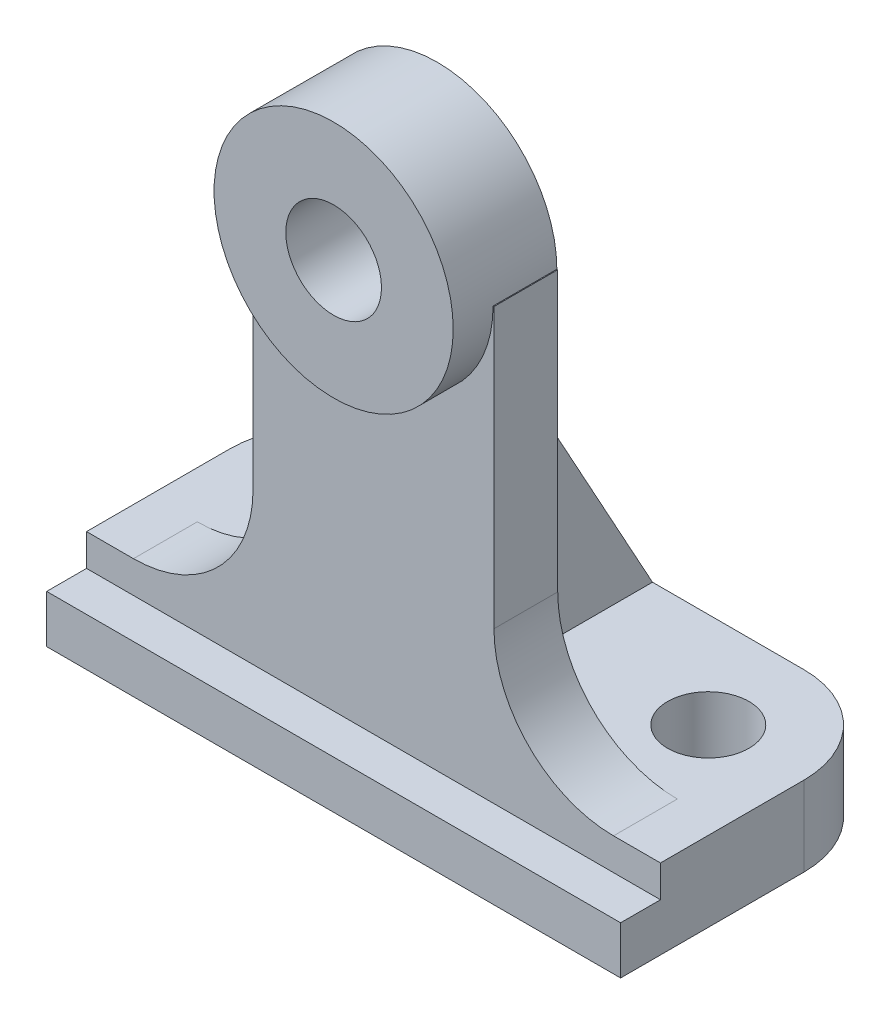
SolidWorks part; units mm, degrees
ref_plane "Front Plane" through (0, 0, 0) normal (0, 0, 1) x (1, 0, 0)
ref_plane "Top Plane" through (0, 0, 0) normal (0, 1, 0) x (1, 0, 0)
ref_plane "Right Plane" through (0, 0, 0) normal (1, 0, 0) x (0, 0, -1)
sketch "Sketch1" plane through (0, 0, 0) normal (1, 0, 0) x (0, 0, -1)
  line L1 (17.5, -5) -> (-17.5, -5)
  line L2 (17.5, -5) -> (17.5, 5)
  line L3 (17.5, 5) -> (-17.5, 5)
  line L4 (-17.5, -5) -> (-17.5, 5)
  line L5 (0, 5) -> (0, -5) construction
  line L6 (17.5, 0) -> (-17.5, 0) construction
  line L7 (-17.5, 5) -> (-12.5, 5)
  line L8 (-17.5, 5) -> (-17.5, 1)
  line L9 (-17.5, 1) -> (-12.5, 1)
  line L10 (-12.5, 5) -> (-12.5, 1)
  point P0 (0, 0)
  dimension "D1" = 10
  dimension "D2" = 35
  dimension "D3" = 5
  dimension "D4" = 4
extrude "Boss-Extrude1" add sketch "Sketch1" along normal blind 36 and the other way blind 36 contours L3 L10 L9 L4 L1 L2 region at (0, -0.1818, -0.9091)
sketch "Sketch2" plane through (0, 0, 12.5) normal (0, 0, 1) x (1, 0, 0)
  line L0 (0, 29.3775) -> (0, -15.3131) construction
  line L1 (-36, 5) -> (36, 5) construction
  line L2 (15.1114, 55) -> (-15.1114, 55)
  line L3 (15.1114, 55) -> (15.1114, 5)
  line L4 (15.1114, 5) -> (-15.1114, 5)
  line L5 (-15.1114, 55) -> (-15.1114, 5)
  line L6 (0, 5) -> (0, 55) construction
  line L7 (15.1114, 30) -> (-15.1114, 30) construction
  arc A0 (-15.1114, 55) -> (15.1114, 55) centre (0, 55) cw
  circle A1 centre (0, 55) radius 6
  circle A2 centre (0, 55) radius 15
  point P3 (0, 30)
  line M7 (36, 5) -> (-36, 5)
  dimension "D3" = 12
  dimension "D4" = 30
  dimension "D1" = 50
  dimension "D2" = 30.2229
extrude "Boss-Extrude4" add sketch "Sketch2" against normal blind 8 contours A2 L2 L5 L3 M7 | L2 A2 A1 | L2 A2 A1 region at (0, 24.3114, 12.5) region at (0, 47.9062, 12.5) region at (0, 62.0938, 12.5)
sketch "Sketch4" plane through (0, 0, 12.5) normal (0, 0, 1) x (1, 0, 0)
  circle A0 centre (0, 55) radius 15
extrude "Boss-Extrude5" add sketch "Sketch4" along normal blind 5
sketch "Sketch6" plane through (0, 0, 12.5) normal (0, 0, -1) x (-1, 0, 0)
  circle A0 centre (0, 55) radius 6
  dimension "D1" = 12
extrude "Cut-Extrude1" cut sketch "Sketch6" against normal through all
fillet "Fillet2" radius 15 2 edges at (-15.1114, 5, 8.5) (15.1114, 5, 8.5)
fillet "Fillet3" radius 12 2 edges at (36, 0, -17.5) (-36, 0, -17.5)
hole_wizard "M12 Tapped Hole1" positions "Sketch7" profile "Sketch8" tap size "M12" standard "ISO" end condition through all
sketch "Sketch7" plane through (0, 5, 0) normal (0, 1, 0) x (1, 0, 0)
  point P0 (-24, 5.5)
  point P3 (24, 5.5)
sketch "Sketch8" plane through (-24, 5, -5.5) normal (1, 0, 0) x (0, 0, 1)
  line L0 (0, 0) -> (0, 10)
  line L1 (0, 10) -> (5.1, 10)
  line L2 (5.1, 10) -> (5.1, 0)
  line L5 (5.1, 0) -> (0, 0)
  line L11 (0, -6.35) -> (0, 107.95) construction
  dimension "Thru Tap Drill Dia." = 10.2
  dimension "Thru Tap Drill Depth" = 10
cosmetic thread "Hole Thread1" parameters "D2"=12
cosmetic thread "Hole Thread2" parameters "D2"=12
sketch "Sketch9" plane through (0, 0, 0) normal (1, 0, 0) x (0, 0, -1)
  line L0 (17.5, 5) -> (-4.5, 45)
  line L1 (-4.5, 55) -> (-4.5, 20) construction
  dimension "D1" = 40
rib "Rib2" sketch "Sketch9" sketch "Sketch9" thickness 10 extrusion direction parallel to sketch draft on no parameters "D1"=10
